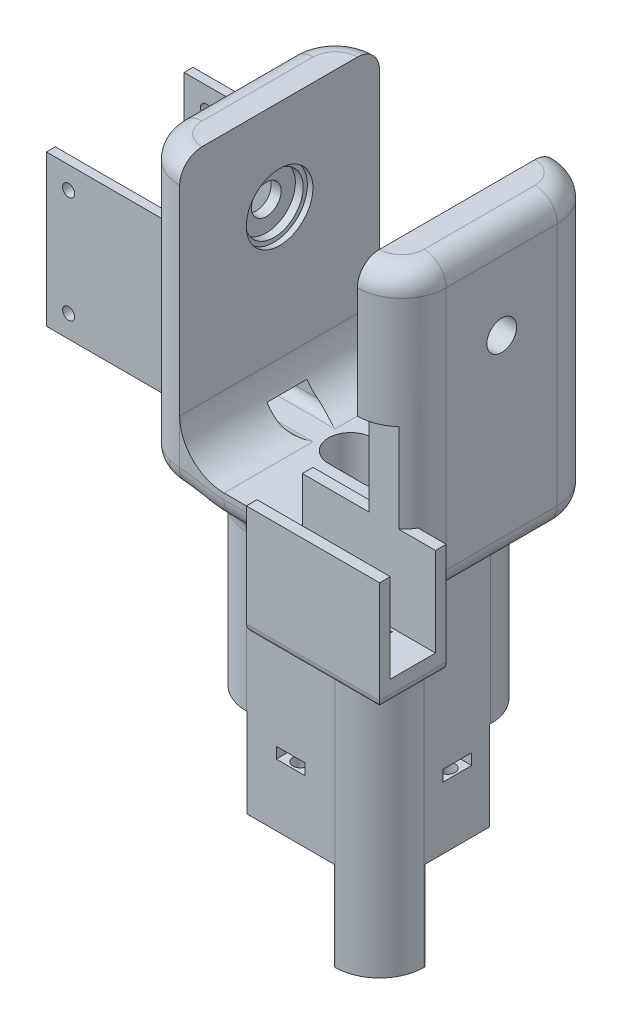
SolidWorks part; units mm, degrees
ref_plane "Plan de face" through (0, 0, 0) normal (0, 0, 1) x (1, 0, 0)
ref_plane "Plan de dessus" through (0, 0, 0) normal (0, 1, 0) x (1, 0, 0)
ref_plane "Plan de droite" through (0, 0, 0) normal (1, 0, 0) x (0, 0, -1)
sketch "Esquisse1" plane through (0, 0, 0) normal (0, 1, 0) x (1, 0, 0)
  line L1 (-20, -17.5) -> (20, -17.5)
  line L2 (-20, -17.5) -> (-20, 17.5)
  line L3 (-20, 17.5) -> (20, 17.5)
  line L4 (20, -17.5) -> (20, 17.5)
  line L5 (-20, -17.5) -> (20, 17.5) construction
  line L6 (-20, 17.5) -> (20, -17.5) construction
  point P0 (0, 0)
  dimension "D1" = 40
  dimension "D2" = 35
extrude "Boss.-Extru.1" add sketch "Esquisse1" along normal blind 80
fillet "Congé1" radius 10 4 edges at (-20, 40, 17.5) (-20, 40, -17.5) (20, 40, -17.5) (20, 40, 17.5)
sketch "Esquisse4" plane through (0, 0, 0) normal (0, -1, 0) x (1, 0, 0)
  line L10 (-20, 17.5) -> (9.8, 17.5)
  line L11 (9.8, 17.5) -> (9.8, 7.3)
  line L12 (9.8, 7.3) -> (20, 7.3)
  line L13 (20, 7.5) -> (20, -7.5) construction
  line L14 (20, 7.3) -> (20, -17.5)
  line L15 (20, -17.5) -> (-9.8, -17.5)
  line L16 (-9.8, -17.5) -> (-9.8, -7.3)
  line L17 (-9.8, -7.3) -> (-20, -7.3)
  line L18 (-20, -7.5) -> (-20, 7.5) construction
  line L19 (-20, -7.3) -> (-20, 17.5)
  line L20 (-10, 17.5) -> (10, 17.5) construction
  line L21 (10, -17.5) -> (-10, -17.5) construction
  arc A2 (-20, -7.5) -> (-10, -17.5) centre (-10, -7.5) ccw construction
  arc A3 (20, 7.5) -> (10, 17.5) centre (10, 7.5) ccw construction
  dimension "D1" = 0.2
  dimension "D2" = 0.2
  dimension "D3" = 0.2
  dimension "D4" = 0.2
extrude "Enlèv. mat.-Extru.3" cut sketch "Esquisse4" against normal blind 20
sketch "Esquisse5" plane through (0, 20, 0) normal (0, -1, 0) x (1, 0, 0)
  line L0 (-20, 7.5) -> (-20, -7.3) construction
  line L9 (-9.8, 7.3) -> (-20, 7.3)
  line L10 (-9.8, 7.3) -> (-9.8, 17.5)
  line L11 (-9.8, 17.5) -> (-20, 17.5)
  line L12 (-20, 7.3) -> (-20, 17.5)
  line L13 (20, -17.5) -> (9.8, -17.5)
  line L14 (20, -17.5) -> (20, -7.3)
  line L15 (20, -7.3) -> (9.8, -7.3)
  line L16 (9.8, -17.5) -> (9.8, -7.3)
  line L17 (9.8, 17.5) -> (-10, 17.5) construction
  line L18 (20, -7.5) -> (20, 7.3) construction
  line L19 (-9.8, -17.5) -> (10, -17.5) construction
  arc A0 (-10, 17.5) -> (-20, 7.5) centre (-10, 7.5) ccw construction
  arc A1 (10, -17.5) -> (20, -7.5) centre (10, -7.5) ccw construction
  dimension "D1" = 0.2
  dimension "D2" = 0.2
  dimension "D3" = 0.2
  dimension "D4" = 0.2
extrude "Enlèv. mat.-Extru.4" cut sketch "Esquisse5" against normal blind 20
sketch "Esquisse6" plane through (0, 80, 0) normal (0, 1, 0) x (1, 0, 0)
  line L1 (-30, -22.5) -> (30, -22.5)
  line L2 (-30, -22.5) -> (-30, 22.5)
  line L3 (-30, 22.5) -> (30, 22.5)
  line L4 (30, -22.5) -> (30, 22.5)
  line L5 (-30, -22.5) -> (30, 22.5) construction
  line L6 (-30, 22.5) -> (30, -22.5) construction
  point P0 (0, 0)
  dimension "D1" = 45
  dimension "D2" = 60
extrude "Boss.-Extru.2" add sketch "Esquisse6" along normal blind 65
fillet "Congé2" radius 10 4 edges at (-30, 112.5, -22.5) (-30, 112.5, 22.5) (30, 112.5, -22.5) (30, 112.5, 22.5)
fillet "Congé5" radius 5 8 edges at (-17.0711, 80, -14.5711) (-17.0711, 80, 14.5711) (-20, 80, 0) (0, 80, -17.5) (17.0711, 80, -14.5711) (20, 80, 0) (17.0711, 80, 14.5711) (0, 80, 17.5)
fillet "Congé7" radius 5 8 edges at (27.0711, 145, -19.5711) (30, 145, 0) (27.0711, 145, 19.5711) (0, 145, 22.5) (-27.0711, 145, 19.5711) (-30, 145, 0) (-27.0711, 145, -19.5711) (0, 145, -22.5)
sketch "Esquisse7" plane through (0, 0, 17.5) normal (0, 0, 1) x (1, 0, 0)
  line L0 (-20, 145) -> (20, 145) construction
  line L1 (-20, 145) -> (20, 145)
  line L2 (-20, 145) -> (-20, 85)
  line L3 (-20, 85) -> (20, 85)
  line L4 (20, 145) -> (20, 85)
  line L5 (30, 140) -> (30, 80) construction
  dimension "D1" = 60
  dimension "D2" = 40
  dimension "D3" = 10
extrude "Enlèv. mat.-Extru.5" cut sketch "Esquisse7" against normal through all and the other way through all
fillet "Congé8" radius 10 2 edges at (20, 85, 0) (-20, 85, 0)
sketch "Esquisse8" plane through (-30, 0, 0) normal (-1, 0, 0) x (0, 0, 1)
  line L0 (-22.5, 140) -> (2.5, 140) construction
  line L1 (-14.5, 138) -> (14.5, 138)
  line L2 (-14.5, 138) -> (-14.5, 89.5)
  line L3 (-14.5, 89.5) -> (14.5, 89.5)
  line L4 (14.5, 138) -> (14.5, 89.5)
  line L5 (-22.5, 140) -> (-22.5, 95) construction
  dimension "D1" = 29
  dimension "D2" = 48.5
  dimension "D3" = 2
  dimension "D4" = 8
extrude "Enlèv. mat.-Extru.6" cut sketch "Esquisse8" against normal blind 4.75
sketch "Esquisse9" plane through (-30, 0, 0) normal (-1, 0, 0) x (0, 0, 1)
  line L0 (-14.5, 138) -> (-14.5, 89.5) construction
  line L1 (-16.5, 125.5) -> (-14.5, 125.5)
  line L2 (-16.5, 125.5) -> (-16.5, 91.5)
  line L3 (-16.5, 91.5) -> (-14.5, 91.5)
  line L4 (-14.5, 125.5) -> (-14.5, 91.5)
  line L5 (16.5, 125.5) -> (14.5, 125.5)
  line L6 (16.5, 125.5) -> (16.5, 91.5)
  line L7 (16.5, 91.5) -> (14.5, 91.5)
  line L8 (14.5, 125.5) -> (14.5, 91.5)
  line L9 (14.5, 89.5) -> (14.5, 138) construction
  line L10 (-12.5, 89.5) -> (12.5, 89.5) construction
  dimension "D1" = 34
  dimension "D2" = 34
  dimension "D3" = 2
  dimension "D4" = 2
  dimension "D5" = 2
  dimension "D6" = 2
extrude "Boss.-Extru.3" add sketch "Esquisse9" along normal blind 26 and the other way blind 5
sketch "Esquisse10" plane through (-25.25, 0, 0) normal (-1, 0, 0) x (0, 0, 1)
  line L0 (-14.5, 89.5) -> (14.5, 89.5) construction
  line L1 (14.5, 89.5) -> (14.5, 138) construction
  circle A0 centre (0, 124.5) radius 3.35
  dimension "D1" = 6.7
  dimension "D2" = 35
  dimension "D3" = 14.5
extrude "Enlèv. mat.-Extru.7" cut sketch "Esquisse10" against normal through all
sketch "Esquisse11" plane through (0, 0, 16.5) normal (0, 0, 1) x (1, 0, 0)
  line L0 (-29.1652, 125.5) -> (-56, 125.5) construction
  line L1 (-56, 91.5) -> (-56, 125.5) construction
  circle A0 centre (-51, 120.5) radius 1.35
  circle A1 centre (-51, 96.5) radius 1.35
  dimension "D1" = 2.7
  dimension "D2" = 2.7
  dimension "D3" = 24
  dimension "D4" = 5
  dimension "D5" = 5
extrude "Enlèv. mat.-Extru.8" cut sketch "Esquisse11" against normal through all
sketch "Esquisse12" plane through (-20, 0, 0) normal (1, 0, 0) x (0, 0, -1)
  circle A0 centre (0, 124.5) radius 6.55
  dimension "D1" = 13.1
extrude "Enlèv. mat.-Extru.9" cut sketch "Esquisse12" against normal blind 3
sketch "Esquisse13" plane through (-20, 0, 0) normal (1, 0, 0) x (0, 0, -1)
  circle A0 centre (0, 124.5) radius 7.5
  dimension "D1" = 15
extrude "Enlèv. mat.-Extru.10" cut sketch "Esquisse13" against normal blind 1.25
sketch "Esquisse14" plane through (20, 0, 0) normal (-1, 0, 0) x (0, 0, 1)
  circle A0 centre (0, 124.5) radius 6.55
  dimension "D1" = 13.1
extrude "Enlèv. mat.-Extru.11" cut sketch "Esquisse14" against normal blind 4
sketch "Esquisse15" plane through (20, 0, 0) normal (-1, 0, 0) x (0, 0, 1)
  circle A0 centre (0, 124.5) radius 7.5
  dimension "D1" = 15
extrude "Enlèv. mat.-Extru.12" cut sketch "Esquisse15" against normal blind 1.25
sketch "Esquisse16" plane through (0, 85, 0) normal (0, 1, 0) x (1, 0, 0)
  line L0 (-4, 0) -> (4, 0) construction
  line L1 (-4, 5) -> (4, 5)
  line L2 (-4, -5) -> (4, -5)
  arc A0 (-4, 5) -> (-4, -5) centre (-4, 0) ccw
  arc A1 (4, -5) -> (4, 5) centre (4, 0) ccw
  point P2 (0, 0)
  dimension "D2" = 5
  dimension "D1" = 8
extrude "Enlèv. mat.-Extru.13" cut sketch "Esquisse16" against normal through all and the other way through all
sketch "Esquisse17" plane through (-30, 0, 0) normal (-1, 0, 0) x (0, 0, 1)
  line L0 (-2.5, 87) -> (2.5, 87) construction
  line L1 (-2.5, 89) -> (2.5, 89)
  line L2 (-2.5, 85) -> (2.5, 85)
  line L5 (22.5, 95) -> (22.5, 80) construction
  line L6 (-14.5, 89.5) -> (14.5, 89.5) construction
  arc A0 (-2.5, 89) -> (-2.5, 85) centre (-2.5, 87) ccw
  arc A1 (2.5, 85) -> (2.5, 89) centre (2.5, 87) ccw
  point P2 (0, 87)
  dimension "D2" = 2
  dimension "D1" = 5
  dimension "D3" = 22.5
  dimension "D4" = 0.5
extrude "Enlèv. mat.-Extru.14" cut sketch "Esquisse17" against normal blind 20
fillet "Congé9" radius 5 12 edges at (0, 80, -22.5) (-27.0711, 80, -19.5711) (-30, 80, 0) (-27.0711, 80, 19.5711) (-15, 80, 22.5) (-15, 80, -22.5) (15, 80, 22.5) (27.0711, 80, 19.5711) (30, 80, 0) (27.0711, 80, -19.5711) (15, 80, -22.5) (0, 80, 22.5)
sketch "Esquisse18" plane through (-30, 0, 0) normal (-1, 0, 0) x (0, 0, 1)
  line L0 (-4.5, 87) -> (-4.5, 89.5)
  line L1 (-14.5, 89.5) -> (14.5, 89.5) construction
  line L2 (-4.5, 89.5) -> (4.5, 89.5)
  line L3 (4.5, 89.5) -> (4.5, 87)
  line L4 (4.5, 87) -> (-4.5, 87)
  arc A0 (-2.5, 89) -> (-2.5, 85) centre (-2.5, 87) ccw construction
  arc A1 (2.5, 85) -> (2.5, 89) centre (2.5, 87) ccw construction
extrude "Enlèv. mat.-Extru.15" cut sketch "Esquisse18" against normal blind 20
sketch "Esquisse19" plane through (0, 20, 0) normal (0, -1, 0) x (-1, 0, 0)
  line L0 (9.8, 17.5) -> (-9.8, 17.5) construction
  circle A0 centre (0, 15.3) radius 1.7
  dimension "D1" = 3.4
  dimension "D2" = 2.2
extrude "Enlèv. mat.-Extru.16" cut sketch "Esquisse19" against normal blind 20
sketch "Esquisse20" plane through (0, 0, -17.5) normal (0, 0, -1) x (-1, 0, 0)
  line L0 (9.8, 20) -> (-9.8, 20) construction
  line L1 (-3.25, 36.5) -> (3.25, 36.5)
  line L2 (-3.25, 36.5) -> (-3.25, 34)
  line L3 (-3.25, 34) -> (3.25, 34)
  line L4 (3.25, 36.5) -> (3.25, 34)
  line L5 (-3.25, 36.5) -> (3.25, 34) construction
  line L6 (-3.25, 34) -> (3.25, 36.5) construction
  point P0 (0, 35.25)
  dimension "D1" = 14
  dimension "D2" = 6.5
  dimension "D3" = 2.5
extrude "Enlèv. mat.-Extru.17" cut sketch "Esquisse20" against normal blind 5.8
sketch "Esquisse21" plane through (0, 20, 0) normal (0, -1, 0) x (1, 0, 0)
  line L0 (-20, 7.3) -> (-20, -7.3) construction
  circle A0 centre (-17.8, 0) radius 1.7
  dimension "D1" = 3.4
  dimension "D2" = 2.2
extrude "Enlèv. mat.-Extru.18" cut sketch "Esquisse21" against normal blind 20
sketch "Esquisse22" plane through (-20, 0, 0) normal (-1, 0, 0) x (0, 0, 1)
  line L0 (7.3, 20) -> (-7.3, 20) construction
  line L1 (-3.25, 36.5) -> (3.25, 36.5)
  line L2 (-3.25, 36.5) -> (-3.25, 34)
  line L3 (-3.25, 34) -> (3.25, 34)
  line L4 (3.25, 36.5) -> (3.25, 34)
  line L5 (-3.25, 36.5) -> (3.25, 34) construction
  line L6 (-3.25, 34) -> (3.25, 36.5) construction
  point P0 (0, 35.25)
  dimension "D1" = 6.5
  dimension "D2" = 2.5
  dimension "D3" = 14
extrude "Enlèv. mat.-Extru.19" cut sketch "Esquisse22" against normal blind 5.8
mirror "Symétrie1" about plane through (0, 0, 0) normal (0, 0, 1) of "Enlèv. mat.-Extru.17", "Enlèv. mat.-Extru.16"
mirror "Symétrie2" about plane through (0, 0, 0) normal (1, 0, 0) of "Enlèv. mat.-Extru.19", "Enlèv. mat.-Extru.18"
sketch "Esquisse24" plane through (0, 0, 17.5) normal (0, 0, 1) x (1, 0, 0)
  line L0 (20, 95) -> (20, 140) construction
  line L1 (5, 95) -> (35, 95)
  line L2 (5, 95) -> (5, 70)
  line L3 (5, 70) -> (35, 70)
  line L4 (35, 95) -> (35, 70)
  dimension "D1" = 30
  dimension "D2" = 25
  dimension "D3" = 15
  dimension "D4" = 10
extrude "Boss.-Extru.4" add sketch "Esquisse24" along normal blind 15
sketch "Esquisse25" plane through (35, 0, 0) normal (1, 0, 0) x (0, 0, -1)
  line L0 (-32.5, 95) -> (-17.5, 95) construction
  line L2 (-30.1, 95) -> (-30.1, 75)
  line L3 (-30.1, 75) -> (-19.9, 75)
  line L4 (-19.9, 99.1094) -> (-19.9, 75)
  line L5 (-32.5, 70) -> (-32.5, 95) construction
  line L8 (-30.1, 95) -> (-30.1, 115)
  line L9 (-30.1, 115) -> (-19.9, 115)
  line L10 (-19.9, 99.1094) -> (-19.9, 115)
  dimension "D1" = 10.2
  dimension "D2" = 20
  dimension "D3" = 2.4
  dimension "D4" = 20
extrude "Enlèv. mat.-Extru.20" cut sketch "Esquisse25" against normal blind 30
fillet "Congé11" radius 2 3 edges at (5, 70, 25) (35, 70, 25) (20, 70, 32.5)
sketch "Esquisse26" plane through (0, 75, 0) normal (0, 1, 0) x (1, 0, 0)
  line L0 (5, -30.1) -> (5, -19.9) construction
  line L1 (20, -20.6) -> (26, -20.6)
  line L2 (20, -20.6) -> (20, -29.6)
  line L3 (20, -29.6) -> (26, -29.6)
  line L4 (26, -20.6) -> (26, -29.6)
  line L5 (5, -30.1) -> (35, -30.1) construction
  dimension "D1" = 15
  dimension "D2" = 6
  dimension "D3" = 9
  dimension "D4" = 0.5
extrude "Enlèv. mat.-Extru.21" cut sketch "Esquisse26" against normal blind 30
equation "\"1.25.00mm\"=4"
